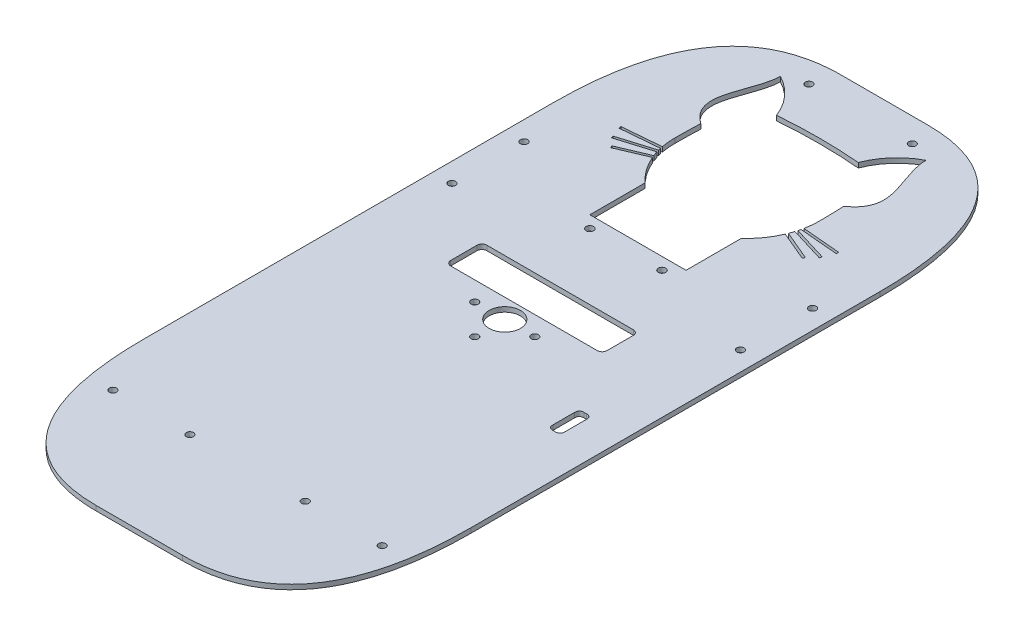
SolidWorks part; units mm, degrees
ref_plane "Спереди" through (0, 0, 0) normal (0, 0, 1) x (1, 0, 0)
ref_plane "Сверху" through (0, 0, 0) normal (0, 1, 0) x (1, 0, 0)
ref_plane "Справа" through (0, 0, 0) normal (1, 0, 0) x (0, 0, -1)
sketch "Эскиз1" plane through (0, 0, 0) normal (0, 1, 0) x (1, 0, 0)
  line L0 (0, 145) -> (0, -165) construction
  line L1 (-68, 145) -> (68, 145)
  line L2 (-68, 145) -> (-68, -165)
  line L3 (-68, -165) -> (68, -165)
  line L4 (68, 145) -> (68, -165)
  line L5 (-68, 0) -> (68, 0) construction
  dimension "D1" = 136
  dimension "D2" = 145
  dimension "D3" = 165
extrude "тело" add sketch "Эскиз1" along normal blind 2
sketch "Эскиз12" plane through (0, 2, 0) normal (0, 1, 0) x (1, 0, 0)
  line L0 (0, 145) -> (0, -165) construction
  line L1 (68, 145) -> (-68, 145) construction
  line L2 (-68, -165) -> (68, -165) construction
  line L3 (60, 55) -> (60, 25) construction
  line L4 (60, 40) -> (-60, 40) construction
  line L5 (-60, 55) -> (-60, 25) construction
  circle A0 centre (60, 55) radius 1.5
  circle A1 centre (-60, 55) radius 1.5
  circle A2 centre (-60, 25) radius 1.5
  circle A3 centre (60, 25) radius 1.5
  point P12 (-60, 40)
  point P17 (0, 40)
  dimension "D2" = 3
  dimension "D1" = 30
  dimension "D3" = 60
  dimension "D4" = 40
extrude "крепление подвески" cut sketch "Эскиз12" against normal through all
sketch "Эскиз8" plane through (0, 2, 0) normal (0, 1, 0) x (1, 0, 0)
  line L0 (-20, -130) -> (20, -130) construction
  line L1 (0, -165) -> (0, 145) construction
  line L2 (-68, -165) -> (68, -165) construction
  line L3 (68, 145) -> (-68, 145) construction
  circle A0 centre (-20, -130) radius 1.5
  circle A1 centre (20, -130) radius 1.5
  point P10 (0, -130)
  dimension "D1" = 3
  dimension "D2" = 40
  dimension "D3" = 130
extrude "крепление камеры" [suppressed] cut sketch "Эскиз8" against normal through all and the other way through all
sketch "Эскиз13" plane through (0, 2, 0) normal (0, 1, 0) x (1, 0, 0)
  line L0 (0, 145) -> (0, -165) construction
  line L1 (68, 145) -> (-68, 145) construction
  line L2 (-68, -165) -> (68, -165) construction
  line L3 (-57, 100) -> (57, 100) construction
  line L4 (-68, -10) -> (68, -10) construction
  line L5 (-57, -35) -> (57, -35) construction
  line L6 (-68, 145) -> (-68, -165) construction
  line L7 (-57, -110) -> (57, -110) construction
  line L8 (68, -165) -> (68, 145) construction
  line L9 (-25, 100) -> (-57, 100) construction
  line L10 (25, 100) -> (57, 100) construction
  line L11 (-57, -35) -> (-25, -35) construction
  line L12 (25, -35) -> (57, -35) construction
  line L13 (-57, -110) -> (-25, -110) construction
  line L14 (25, -110) -> (57, -110) construction
  circle A0 centre (-57, 100) radius 1.5
  circle A1 centre (57, 100) radius 1.5
  circle A2 centre (57, -35) radius 1.5
  circle A3 centre (-57, -35) radius 1.5
  circle A4 centre (-57, -110) radius 1.5
  circle A5 centre (57, -110) radius 1.5
  circle A6 centre (-25, 100) radius 1.5
  circle A7 centre (25, 100) radius 1.5
  circle A8 centre (25, -35) radius 1.5
  circle A9 centre (-25, -35) radius 1.5
  circle A10 centre (-25, -110) radius 1.5
  circle A11 centre (25, -110) radius 1.5
  point P18 (0, 100)
  point P19 (0, -35)
  point P20 (0, -110)
  point P27 (0, -10)
  dimension "D1" = 3
  dimension "D2" = 110
  dimension "D3" = 25
  dimension "D4" = 100
  dimension "D5" = 114
  dimension "D6" = 32
  dimension "D7" = 32
  dimension "D8" = 32
  dimension "D9" = 32
  dimension "D10" = 32
  dimension "D11" = 32
extrude "крепления уголков" [suppressed] cut sketch "Эскиз13" against normal through all
sketch "Эскиз9" plane through (0, 2, 0) normal (0, 1, 0) x (1, 0, 0)
  line L0 (0, -50) -> (0, 50) construction
  line L2 (-68, -165) -> (68, -165) construction
  circle A0 centre (0, -13) radius 6.5
  circle A1 centre (0, -13) radius 12.5 construction
  circle A2 centre (0, -0.5) radius 1.5
  circle A3 centre (12.5, -13) radius 1.5
  circle A4 centre (-12.5, -13) radius 1.5
  circle A5 centre (0, -25.5) radius 1.5
  dimension "D2" = 13
  dimension "D3" = 25
  dimension "D4" = 3
  dimension "D1" = 152
extrude "ось вращения качалки" cut sketch "Эскиз9" against normal through all
sketch "Эскиз5" plane through (0, 2, 0) normal (0, 1, 0) x (1, 0, 0)
  line L0 (-50, -100) -> (50, -60) construction
  line L1 (-50, -60) -> (50, -60) construction
  line L2 (-50, -60) -> (-50, -100) construction
  line L3 (-50, -100) -> (50, -100) construction
  line L4 (50, -60) -> (50, -100) construction
  line L5 (-50, -60) -> (50, -100) construction
  line L6 (-68, -165) -> (68, -165) construction
  circle A0 centre (-50, -60) radius 1.5
  circle A1 centre (50, -60) radius 1.5
  circle A2 centre (50, -100) radius 1.5
  circle A3 centre (-50, -100) radius 1.5
  point P12 (0, -80)
  dimension "D1" = 3
  dimension "D2" = 100
  dimension "D3" = 40
  dimension "D4" = 65
extrude "крепление raspberry" [suppressed] cut sketch "Эскиз5" against normal through all
sketch "Эскиз11" plane through (0, 2, 0) normal (0, 1, 0) x (1, 0, 0)
  line L0 (-32.5, 2.5) -> (32.5, 2.5) construction
  line L1 (-32.5, 10) -> (32.5, 10)
  line L2 (-32.5, 10) -> (-32.5, -5)
  line L3 (-32.5, -5) -> (32.5, -5)
  line L4 (32.5, 10) -> (32.5, -5)
  point P11 (0, 10)
  dimension "D1" = 65
  dimension "D2" = 15
extrude "отверстие под провода на нижний этаж" cut sketch "Эскиз11" against normal through all
fillet "Скругление3" radius 2 4 edges at (-32.5, 1, 5) (32.5, 1, 5) (32.5, 1, -10) (-32.5, 1, -10)
sketch "Эскиз14" [suppressed] plane through (0, 2, 0) normal (0, 1, 0) x (1, 0, 0)
  line L0 (0, 160) -> (0, -130) construction
  line L1 (68, 160) -> (-68, 160) construction
  line L2 (-68, -130) -> (68, -130) construction
  line L3 (-47.5, -125) -> (47.5, -125) construction
  line L4 (47.5, -115) -> (47.5, -135) construction
  line L5 (-12.5, -95) -> (12.5, -95) construction
  line L6 (-47.5, -115) -> (-47.5, -135) construction
  circle A0 centre (-47.5, -115) radius 1.5
  circle A1 centre (-47.5, -135) radius 1.5
  circle A2 centre (47.5, -115) radius 1.5
  circle A3 centre (47.5, -135) radius 1.5
  point P8 (0, -125)
  point P14 (-47.5, -125)
  point P15 (47.5, -125)
  dimension "D1" = 3
  dimension "D2" = 20
  dimension "D3" = 30
  dimension "D4" = 95
extrude "крепление стопоров" [suppressed] cut sketch "Эскиз14" against normal through all
sketch "Эскиз15" plane through (0, 2, 0) normal (0, 1, 0) x (1, 0, 0)
  line L0 (-21.5, 135) -> (21.5, 135) construction
  line L1 (68, 145) -> (-68, 145) construction
  circle A0 centre (21.5, 135) radius 1.5
  circle A1 centre (-21.5, 135) radius 1.5
  point P6 (0, 135)
  dimension "D1" = 3
  dimension "D2" = 10
  dimension "D3" = 43
extrude "Крепление фронтальной камеры" cut sketch "Эскиз15" against normal up to next
sketch "Эскиз16" plane through (0, 2, 0) normal (0, 1, 0) x (1, 0, 0)
  line L0 (-56, -120) -> (-24, -120) construction
  line L1 (-68, -165) -> (68, -165) construction
  line L2 (-68, 145) -> (-68, -165) construction
  line L3 (0, -165) -> (0, 145) construction
  line L4 (68, 145) -> (-68, 145) construction
  circle A0 centre (-56, -120) radius 1.5
  circle A1 centre (-24, -120) radius 1.5
  circle A2 centre (24, -120) radius 1.5
  circle A3 centre (56, -120) radius 1.5
  dimension "D1" = 32
  dimension "D4" = 3
  dimension "D2" = 45
  dimension "D3" = 12
extrude "Крепление силовых уголков со стороны буллета" cut sketch "Эскиз16" against normal up to next
sketch "Эскиз17" plane through (0, 2, 0) normal (0, 1, 0) x (1, 0, 0)
  line L1 (48, -30) -> (53, -30)
  line L2 (48, -30) -> (48, -43)
  line L3 (48, -43) -> (53, -43)
  line L4 (53, -30) -> (53, -43)
  dimension "D2" = 13
  dimension "D3" = 5
extrude "Отверстие по дпитание сервоприводов и шилда" cut sketch "Эскиз17" against normal up to next
sketch "Эскиз18" plane through (0, 2, 0) normal (0, 1, 0) x (1, 0, 0)
  line L0 (0, 0) -> (0, 145) construction
  line L1 (68, 145) -> (-68, 145) construction
  line L2 (-20, 42.3884) -> (20, 42.3884)
  line L3 (20, 42.3884) -> (20, 65.3884)
  line L5 (-20, 65.3884) -> (-20, 42.3884)
  line L6 (10, 42.3884) -> (10, 27.3884)
  line L7 (10, 27.3884) -> (-10, 27.3884)
  line L8 (-10, 27.3884) -> (-10, 42.3884)
  line L9 (28.2843, 77.7491) -> (-28.2843, 77.7491)
  line L11 (-29.2321, 81.0049) -> (-45.2082, 79.623)
  line L12 (15, 37.3884) -> (-15, 37.3884) construction
  line L13 (-28.6978, 79.0063) -> (-43.2061, 74.5863)
  line L16 (-27.6267, 76.0544) -> (-39.8248, 70.8909)
  line L17 (-29.4421, 81.9904) -> (-45.2944, 80.6193)
  line L18 (-28.9733, 79.9677) -> (-43.4975, 75.5429)
  line L19 (-28.0012, 76.9818) -> (-40.2146, 71.8117)
  line L20 (-45.2944, 80.6193) -> (-45.2082, 79.623)
  line L21 (-43.4975, 75.5429) -> (-43.2061, 74.5863)
  line L22 (-40.2146, 71.8117) -> (-39.8248, 70.8909)
  line L23 (-29.3183, 82.0011) -> (-45.2944, 80.6193) construction
  line L24 (-28.6818, 79.0111) -> (-43.2061, 74.5863) construction
  line L25 (-27.6114, 76.0609) -> (-39.8248, 70.8909) construction
  line L26 (40.2146, 71.8117) -> (39.8248, 70.8909)
  line L27 (43.4975, 75.5429) -> (43.2061, 74.5863)
  line L28 (45.2944, 80.6193) -> (45.2082, 79.623)
  line L29 (28.0012, 76.9818) -> (40.2146, 71.8117)
  line L30 (28.9733, 79.9677) -> (43.4975, 75.5429)
  line L31 (29.4421, 81.9904) -> (45.2944, 80.6193)
  line L32 (27.6267, 76.0544) -> (39.8248, 70.8909)
  line L33 (28.6978, 79.0063) -> (43.2061, 74.5863)
  line L34 (29.2321, 81.0049) -> (45.2082, 79.623)
  arc A0 (20, 65.3884) -> (-20, 65.3884) centre (0, 87.7491) ccw construction
  circle A1 centre (15, 37.3884) radius 1.55
  circle A2 centre (-15, 37.3884) radius 1.55
  arc A4 (-30, 87.7491) -> (-28.2843, 115.7491) centre (199.3322, 87.7491) cw
  arc A5 (-28.2843, 115.7491) -> (28.2843, 115.7491) centre (0, -83.2509) cw
  arc A6 (28.2843, 115.7491) -> (30, 87.7491) centre (-199.3322, 87.7491) cw
  arc A7 (-20, 65.3884) -> (-27.6267, 76.0544) centre (0, 87.7491) cw
  arc A8 (20, 65.3884) -> (27.6267, 76.0544) centre (0, 87.7491) ccw
  arc A9 (29.4421, 81.9904) -> (30, 87.7491) centre (0, 87.7491) ccw
  arc A10 (-30.2864, 131.9093) -> (-16.9975, 117.0291) centre (-43.1419, 107.0545) cw
  arc A11 (30.2864, 131.9093) -> (16.9975, 117.0291) centre (43.1419, 107.0545) ccw
  arc A12 (28.9733, 79.9677) -> (29.2321, 81.0049) centre (0, 87.7491) ccw
  arc A13 (28.0012, 76.9818) -> (28.6978, 79.0063) centre (0, 87.7491) ccw
  arc A14 (-28.0012, 76.9818) -> (-28.6978, 79.0063) centre (0, 87.7491) cw
  arc A15 (-28.9733, 79.9677) -> (-29.2321, 81.0049) centre (0, 87.7491) cw
  arc A16 (-29.4421, 81.9904) -> (-30, 87.7491) centre (0, 87.7491) cw
  spline S0 degree 3 poles (-29.7583, 98.2745) (-43.0929, 107.4905) (-30.2542, 120.6232) (-30.2864, 131.9093) knots 0 0 0 0 1 1 1 1
  spline S1 degree 3 poles (29.7583, 98.2745) (43.0929, 107.4905) (30.2542, 120.6232) (30.2864, 131.9093) knots 0 0 0 0 1 1 1 1
  point P9 (0, 27.3884)
  point P15 (0, 42.3884)
  point P16 (0, 0)
  point P25 (0, 37.3884)
  point P26 (0, 0)
  point P56 (0, 0)
  dimension "D6" = 60
  dimension "D8" = 3.1
  dimension "D1" = 40
  dimension "D2" = 20
  dimension "D3" = 15
  dimension "D4" = 23
  dimension "D5" = 10
  dimension "D7" = 12
  dimension "D9" = 5
  dimension "D10" = 30
  dimension "D11" = 38
  dimension "D12" = 56.5685
  dimension "D16" = 6
  dimension "D13" = 1
  dimension "D14" = 1
  dimension "D15" = 1
fillet "Скругление4" radius 50 2 edges at (68, 1, 165) (-68, 1, -145) second distance 70 conic rho 0.5 first distance on face at (0, 1, 165) first distance on face at (0, 1, -145)
fillet "Скругление5" radius 70 2 edges at (-68, 1, 165) (68, 1, -145) second distance 50 conic rho 0.5 first distance on face at (-68, 1.25, -15) first distance on face at (68, 1.25, 35)
fillet "Скругление6" radius 2 4 edges at (48, 1, 43) (53, 1, 43) (48, 1, 30) (53, 1, 30) conic rho 0.5
sketch "Эскиз19" plane through (0, 2, 0) normal (0, 1, 0) x (1, 0, 0)
  line L1 (-95.3857, 162.9355) -> (76.7354, 162.9355)
  line L2 (-95.3857, 162.9355) -> (-95.3857, 60)
  line L3 (-95.3857, 60) -> (76.7354, 60)
  line L4 (76.7354, 162.9355) -> (76.7354, 60)
  circle A0 centre (-60, 55) radius 1.5 construction
  dimension "D1" = 5
extrude "Вырез-Вытянуть3" [suppressed] cut sketch "Эскиз19" against normal up to next
fillet "Скругление8" [suppressed] radius 10
extrude "Вырез под манипулятор" cut sketch "Эскиз18" against normal up to next contours S0 A4 A5 A10 | A6 S1 A11 A5 | A16 L17 L20 L11 A15 L18 L21 L13 A14 L9 A13 L33 L27 L30 A12 L34 L28 L31 A9 A6 A5 A4 | A14 L19 L22 L16 A7 L5 L2 L3 A8 L32 L26 L29 A13 L9 | A1 | A2 region at (0, 2, -61.3278) region at (0, 2, -96.8323) region at (-28.5376, 2, -116.8678) region at (28.5376, 2, -116.8678) region at (15, 2, -37.3884) region at (-15, 2, -37.3884)
